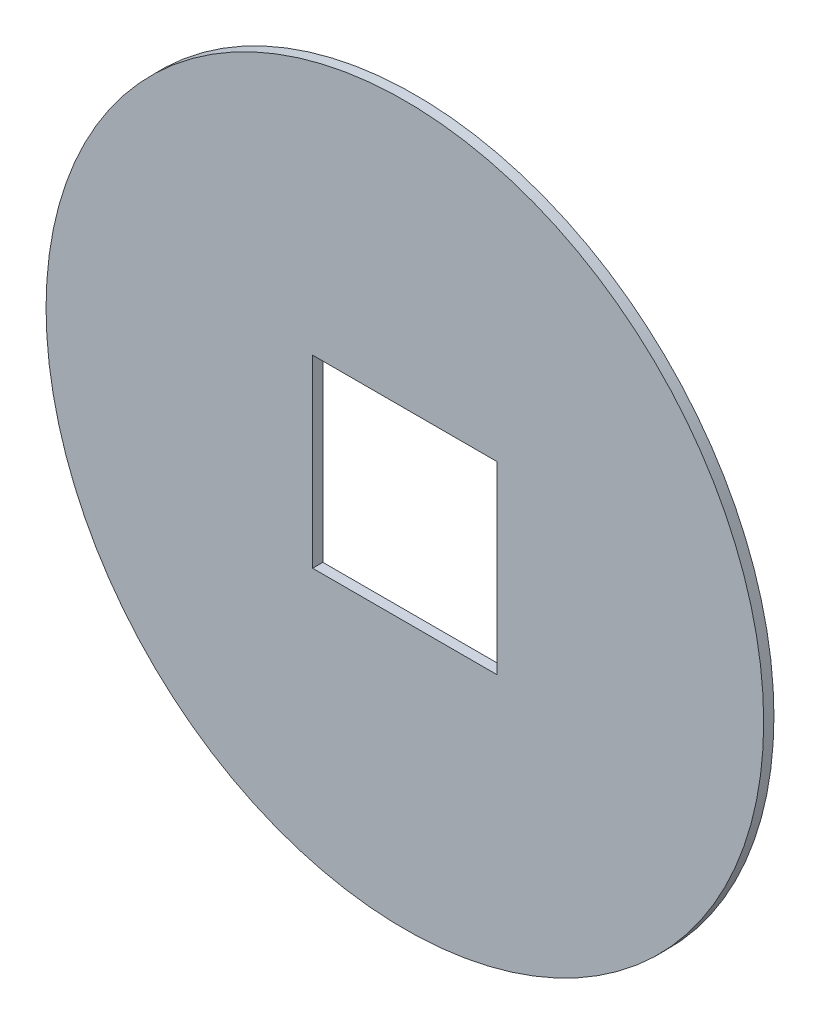
SolidWorks part; units mm, degrees
material "Balsa"
ref_plane "Plan de face" through (0, 0, 0) normal (0, 0, 1) x (1, 0, 0)
ref_plane "Plan de dessus" through (0, 0, 0) normal (0, 1, 0) x (1, 0, 0)
ref_plane "Plan de droite" through (0, 0, 0) normal (1, 0, 0) x (0, 0, -1)
sketch "Esquisse1" plane through (0, 0, 0) normal (0, 0, 1) x (1, 0, 0)
  line L0 (45, 45) -> (45, -45)
  line L1 (45, -45) -> (-45, -45)
  line L2 (-45, -45) -> (-45, 45)
  line L3 (-45, 45) -> (45, 45)
  line L8 (45, -45) -> (-45, 45) construction
  line L9 (-45, -45) -> (45, 45) construction
  circle A0 centre (0, 0) radius 175
  dimension "D2" = 350
  dimension "D3" = 90
  dimension "D1" = 90
extrude "Boss.-Extru.1" add sketch "Esquisse1" along normal blind 5
